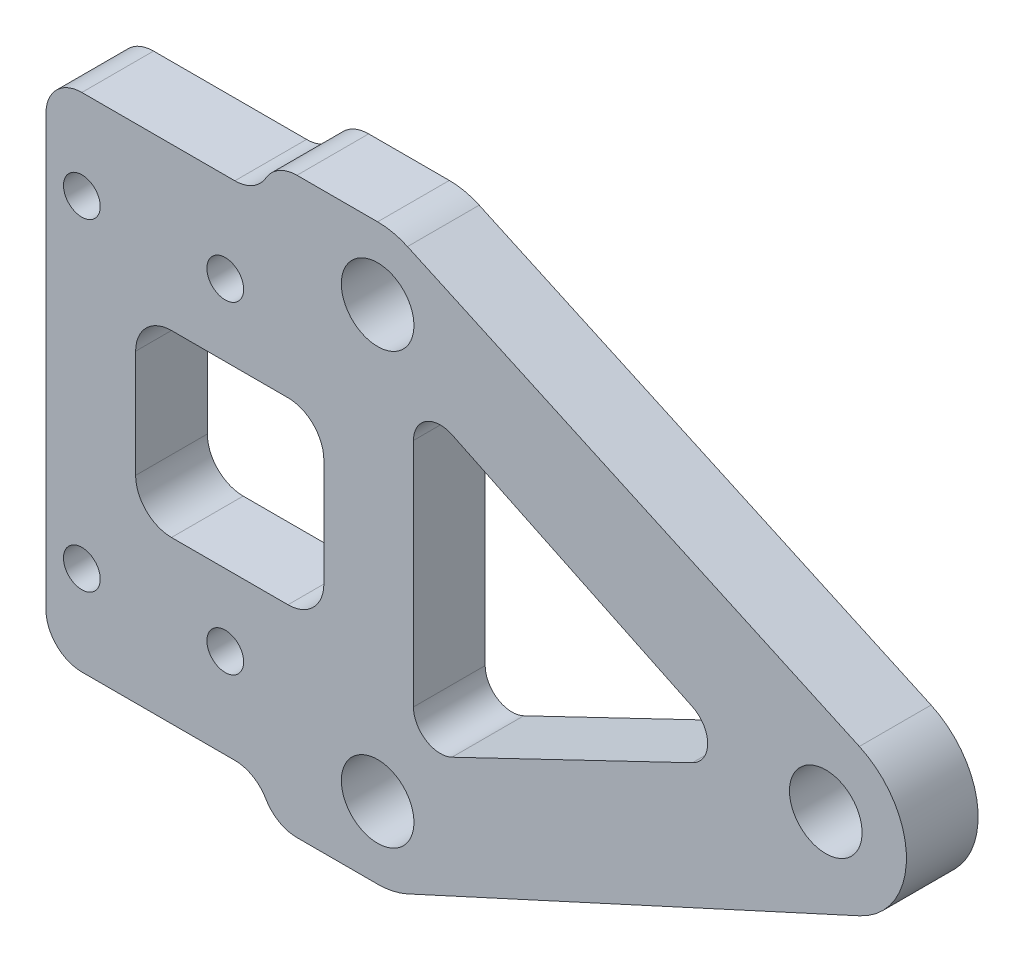
SolidWorks part; units mm, degrees
material "Thornel Mat VMA"
ref_plane "前视基准面" through (0, 0, 0) normal (0, 0, 1) x (1, 0, 0)
ref_plane "上视基准面" through (0, 0, 0) normal (0, 1, 0) x (1, 0, 0)
ref_plane "右视基准面" through (0, 0, 0) normal (1, 0, 0) x (0, 0, -1)
other "Configuration Table"
sketch "草图1" plane through (0, 0, 0) normal (0, 0, 1) x (1, 0, 0)
  line L1 (-24, -16) -> (24, -16)
  line L2 (-24, -16) -> (-24, 16)
  line L3 (-24, 16) -> (24, 16)
  line L4 (24, -16) -> (24, 16)
  line L5 (-24, -16) -> (24, 16) construction
  line L6 (-24, 16) -> (24, -16) construction
  point P0 (0, 0)
  dimension "D1" = 48
  dimension "D2" = 32
extrude "凸台-拉伸1" add sketch "草图1" along normal blind 4
sketch "草图2" plane through (0, 0, 0) normal (0, 0, -1) x (-1, 0, 0)
  circle A0 centre (5.5, -12) radius 2.025 construction
  circle A1 centre (-19.5, 0) radius 2.025 construction
  circle A2 centre (5.5, 12) radius 2.025 construction
  circle A3 centre (5.5, -12) radius 2.025 construction
  circle A4 centre (-19.5, 0) radius 2.025 construction
  circle A5 centre (5.5, 12) radius 2.025 construction
  circle A6 centre (22, -9) radius 0.8 construction
  circle A7 centre (14, -9) radius 0.8 construction
  circle A8 centre (22, -9) radius 0.8 construction
  circle A9 centre (14, -9) radius 0.8 construction
  circle A10 centre (-19.5, 0) radius 2.025
  circle A11 centre (5.5, -12) radius 2.025
  circle A12 centre (5.5, 12) radius 2.025
  circle A13 centre (14, -9) radius 1.025
  circle A14 centre (22, -9) radius 1.025
  dimension "D1" = 4.05
  dimension "D2" = 2.05
extrude "切除-拉伸1" cut sketch "草图2" against normal blind 30.8
sketch "草图4" plane through (0, 0, 0) normal (0, 0, -1) x (-1, 0, 0)
  line L1 (-24, -16) -> (-24, 16) construction
  line L2 (-24, 16) -> (24, 16) construction
  line L3 (-21.3738, 4.0913) -> (3.8344, 15.6367)
  line L4 (5.5, 16) -> (-24, 16)
  line L5 (-24, 16) -> (-24, 0)
  arc A0 (-21.3738, 4.0913) -> (-24, 0) centre (-19.5, 0) ccw
  arc A1 (5.5, 16) -> (3.8344, 15.6367) centre (5.5, 12) ccw
extrude "切除-拉伸2" cut sketch "草图4" against normal blind 10
mirror "镜向1" about plane through (0, 0, 0) normal (0, 1, 0) of "切除-拉伸2"
sketch "草图5" plane through (0, 0, 0) normal (0, 0, -1) x (-1, 0, 0)
  line L0 (0, 0) -> (29.8676, 0) construction
  line L1 (24, -16) -> (12, -16)
  line L2 (24, -16) -> (24, -14)
  line L3 (24, -14) -> (12, -14)
  line L4 (12, -16) -> (12, -14)
  line L6 (12, 16) -> (12, 14)
  line L7 (24, 14) -> (12, 14)
  line L8 (24, 16) -> (24, 14)
  line L9 (24, 16) -> (12, 16)
  point P8 (29.8676, 0)
  dimension "D1" = 14
  dimension "D2" = 12
extrude "切除-拉伸3" cut sketch "草图5" against normal blind 10
fillet "圆角1" radius 2 4 edges at (-24, -14, 2) (-24, 14, 2) (-12, -16, 2) (-12, 16, 2)
sketch "草图6" plane through (0, 0, 0) normal (0, 0, -1) x (-1, 0, 0)
  line L0 (5.5, 12) -> (-19.5, 0) construction
  line L1 (-19.5, 0) -> (5.5, -12) construction
  line L2 (5.5, -12) -> (5.5, 12) construction
  line L3 (3.5, 8.8215) -> (-14.8782, 0)
  line L4 (-14.8782, 0) -> (3.5, -8.8215)
  line L5 (3.5, -8.8215) -> (3.5, 8.8215)
  dimension "D1" = 2
extrude "切除-拉伸4" cut sketch "草图6" against normal blind 10
fillet "圆角2" radius 1.5 3 edges at (-3.5, 8.8215, 2) (-3.5, -8.8215, 2) (14.8782, 0, 2)
mirror "镜向2" about plane through (0, 0, 0) normal (0, 1, 0) of "切除-拉伸1"
sketch "草图7" plane through (0, 0, 0) normal (0, 0, -1) x (-1, 0, 0)
  line L0 (0, 0) -> (13.75, 0) construction
  line L1 (8.5, -5) -> (19, -5)
  line L2 (8.5, -5) -> (8.5, 5)
  line L3 (8.5, 5) -> (19, 5)
  line L4 (19, -5) -> (19, 5)
  line L5 (8.5, -5) -> (19, 5) construction
  line L6 (8.5, 5) -> (19, -5) construction
  line L7 (24, 12) -> (24, -12) construction
  line L8 (3.5, -6.4377) -> (3.5, 6.4377) construction
  circle A0 centre (22, 9) radius 1.025 construction
  point P0 (13.75, 0)
  dimension "D1" = 4
  dimension "D2" = 5
  dimension "D3" = 5
extrude "切除-拉伸5" cut sketch "草图7" against normal blind 10
fillet "圆角3" radius 2 6 edges at (-12, 14, 2) (-12, -14, 2) (-8.5, 5, 2) (-19, 5, 2) (-19, -5, 2) (-8.5, -5, 2)
